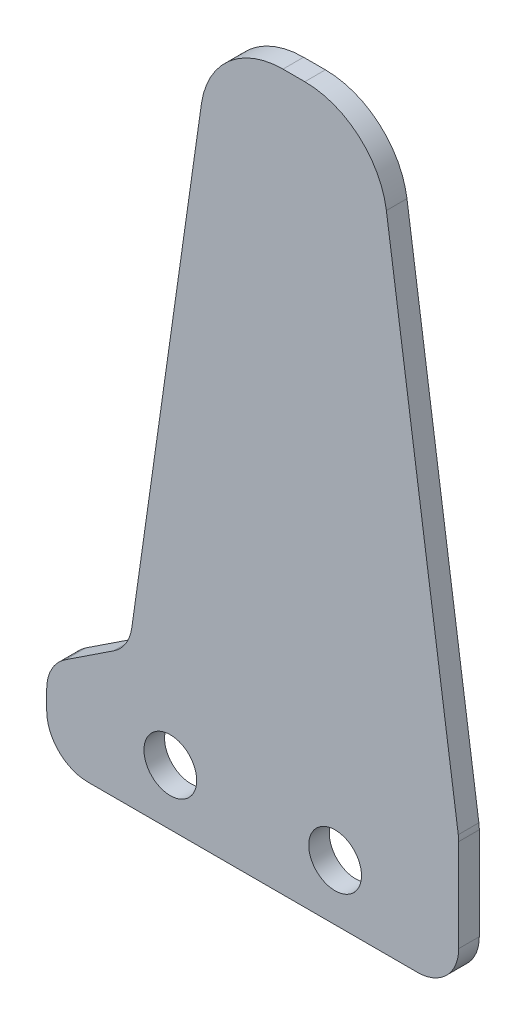
SolidWorks part; units mm, degrees
ref_plane "Front Plane" through (0, 0, 0) normal (0, 0, 1) x (1, 0, 0)
ref_plane "Top Plane" through (0, 0, 0) normal (0, 1, 0) x (1, 0, 0)
ref_plane "Right Plane" through (0, 0, 0) normal (1, 0, 0) x (0, 0, -1)
sketch "Sketch1" plane through (0, 0, 0) normal (0, 0, 1) x (1, 0, 0)
  line L0 (9.525, -4.3042) -> (9.525, 6.236)
  line L1 (9.525, 6.236) -> (3.175, 50.8)
  line L2 (3.175, 50.8) -> (-9.525, 50.8)
  line L3 (-9.525, 50.8) -> (-15.875, 6.236)
  line L5 (-22.225, -4.3042) -> (9.525, -4.3042)
  line L6 (9.525, -3.846) -> (9.525, 5.8751) construction
  line L7 (-23.2553, -4.3042) -> (9.525, -4.3042) construction
  line L8 (-13.3488, 6.236) -> (11.3285, 6.236) construction
  line L9 (-15.875, 6.236) -> (-22.225, 2.0458)
  line L10 (-22.225, 2.0458) -> (-22.225, -4.3042)
  circle A0 centre (0, 0) radius 2.032
  circle A1 centre (-12.7, 0) radius 2.032
  circle A2 centre (-12.7, 0) radius 1.905 construction
  dimension "D1" = 4.064
  dimension "D2" = 50.8
  dimension "D3" = 31.75
  dimension "D4" = 12.7
  dimension "D5" = 6.35
  dimension "D6" = 25.4
extrude "Boss-Extrude1" add sketch "Sketch1" along normal blind 1.5875
fillet "Fillet1" radius 6.35 2 edges at (-9.525, 50.8, 0.7937) (3.175, 50.8, 0.7937)
fillet "Fillet2" radius 3.175 5 edges at (9.525, 6.236, 0.7937) (9.525, -4.3042, 0.7937) (-22.225, -4.3042, 0.7937) (-22.225, 2.0458, 0.7937) (-15.875, 6.236, 0.7937)
